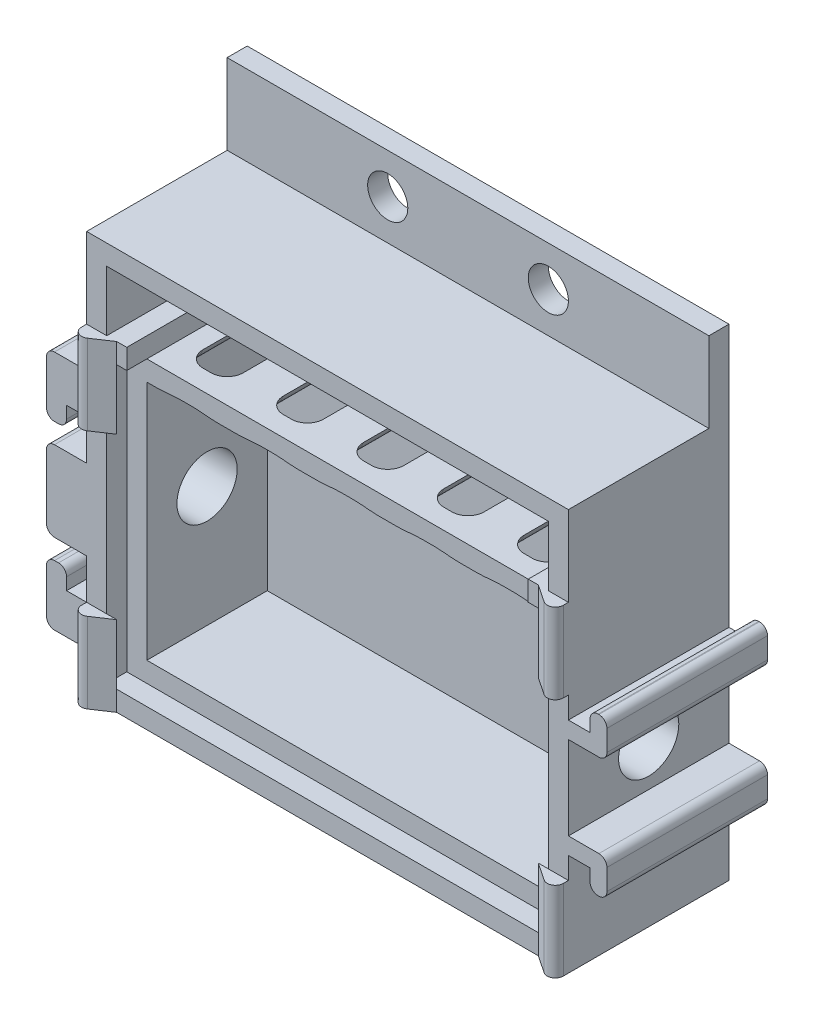
SolidWorks part; units mm, degrees
ref_plane "Front Plane" through (0, 0, 0) normal (0, 0, 1) x (1, 0, 0)
ref_plane "Top Plane" through (0, 0, 0) normal (0, 1, 0) x (1, 0, 0)
ref_plane "Right Plane" through (0, 0, 0) normal (1, 0, 0) x (0, 0, -1)
sketch "Sketch1" plane through (0, 0, 0) normal (0, 0, 1) x (1, 0, 0)
  line L1 (0, 0) -> (76.2, 0)
  line L2 (0, 0) -> (0, 76.2)
  line L3 (0, 76.2) -> (76.2, 76.2)
  line L4 (76.2, 0) -> (76.2, 76.2)
  dimension "D1" = 76.2
  dimension "D2" = 76.2
extrude "Boss-Extrude1" add sketch "Sketch1" along normal blind 25.4
sketch "Sketch2" plane through (0, 0, 25.4) normal (0, 0, 1) x (1, 0, 0)
  line L0 (0, 76.2) -> (0, 0) construction
  line L1 (3.175, 3.175) -> (73.025, 3.175)
  line L2 (3.175, 3.175) -> (3.175, 47.625)
  line L3 (3.175, 47.625) -> (73.025, 47.625)
  line L4 (73.025, 3.175) -> (73.025, 47.625)
  line L5 (38.1, 0) -> (38.1, 76.2) construction
  line L6 (0, 0) -> (76.2, 0) construction
  line L7 (76.2, 76.2) -> (0, 76.2) construction
  dimension "D2" = 3.175
  dimension "D1" = 3.175
  dimension "D3" = 28.575
extrude "Cut-Extrude1" cut sketch "Sketch2" against normal blind 3.175
sketch "Sketch9" plane through (0, 0, 22.225) normal (0, 0, 1) x (1, 0, 0)
  line L4 (69.85, 44.45) -> (6.35, 44.45)
  line L5 (69.85, 44.45) -> (6.35, 44.45)
  line L8 (6.35, 44.45) -> (6.35, 6.35)
  line L9 (6.35, 6.35) -> (69.85, 6.35)
  line L10 (69.85, 6.35) -> (69.85, 44.45)
  line L12 (6.35, 44.45) -> (6.35, 6.35)
  line L13 (6.35, 6.35) -> (69.85, 6.35)
  line L14 (69.85, 6.35) -> (69.85, 44.45)
  dimension "D1" = 3.175
extrude "Cut-Extrude9" cut sketch "Sketch9" against normal blind 19.05
sketch "Sketch10" plane through (0, 0, 25.4) normal (0, 0, 1) x (1, 0, 0)
  line L0 (76.2, 0) -> (76.2, 76.2) construction
  line L1 (0, 76.2) -> (76.2, 76.2)
  line L2 (0, 76.2) -> (0, 63.5)
  line L3 (0, 63.5) -> (76.2, 63.5)
  line L4 (76.2, 76.2) -> (76.2, 63.5)
  dimension "D1" = 12.7
extrude "Cut-Extrude10" cut sketch "Sketch10" against normal blind 22.225
sketch "Sketch11" plane through (0, 0, 25.4) normal (0, 0, 1) x (1, 0, 0)
  line L0 (38.1, 63.5) -> (38.1, 47.625) construction
  line L1 (3.175, 60.325) -> (73.025, 60.325)
  line L2 (3.175, 60.325) -> (3.175, 50.8)
  line L3 (6.35, 50.8) -> (3.175, 50.8)
  line L4 (73.025, 60.325) -> (73.025, 50.8)
  line L5 (0, 63.5) -> (76.2, 63.5) construction
  line L6 (73.025, 47.625) -> (3.175, 47.625) construction
  line L7 (0, 63.5) -> (0, 0) construction
  line L8 (0, 63.5) -> (76.2, 63.5) construction
  line L9 (6.35, 47.625) -> (6.35, 50.8)
  line L10 (6.35, 47.625) -> (69.85, 47.625)
  line L11 (73.025, 50.8) -> (69.85, 50.8)
  line L12 (6.35, 111.125) -> (95.25, 60.325)
  line L13 (69.85, 47.625) -> (69.85, 50.8)
  line M10 (3.175, 47.625) -> (73.025, 47.625)
  dimension "D1" = 3.175
  dimension "D2" = 3.175
  dimension "D3" = 3.175
  dimension "D4" = 3.175
extrude "Cut-Extrude11" cut sketch "Sketch11" against normal blind 22.225 contours L12 L0 L10 L13 L11 L4 L1 | L0 L1 L2 L3 L9 M10
sketch "Sketch12" plane through (0, 0, 3.175) normal (0, 0, 1) x (1, 0, 0)
  line L0 (38.1, 63.5) -> (38.1, 76.2) construction
  line L1 (0, 63.5) -> (76.2, 63.5) construction
  line L2 (76.2, 76.2) -> (0, 76.2) construction
  line L3 (0, 76.2) -> (0, 63.5) construction
  circle A0 centre (25.4, 69.85) radius 3.175
  circle A1 centre (50.8, 69.85) radius 3.175
  point P8 (0, 69.85)
  dimension "D2" = 6.35
  dimension "D1" = 25.4
  dimension "D3" = 6.35
extrude "Cut-Extrude12" cut sketch "Sketch12" against normal up to next
sketch "Sketch13" plane through (0, 44.45, 0) normal (0, -1, 0) x (1, 0, 0)
  line L0 (6.35, 12.7) -> (69.85, 12.7) construction
  line L1 (12.065, 19.05) -> (13.335, 19.05)
  line L2 (9.525, 16.51) -> (9.525, 8.89)
  line L3 (12.065, 6.35) -> (13.335, 6.35)
  line L4 (15.875, 16.51) -> (15.875, 8.89)
  line L5 (6.35, 3.175) -> (6.35, 22.225) construction
  line L6 (69.85, 3.175) -> (69.85, 22.225) construction
  line L7 (28.575, 16.51) -> (28.575, 8.89)
  line L8 (22.225, 16.51) -> (22.225, 8.89)
  line L9 (24.765, 6.35) -> (26.035, 6.35)
  line L10 (24.765, 19.05) -> (26.035, 19.05)
  line L11 (41.275, 16.51) -> (41.275, 8.89)
  line L12 (34.925, 16.51) -> (34.925, 8.89)
  line L13 (37.465, 6.35) -> (38.735, 6.35)
  line L14 (37.465, 19.05) -> (38.735, 19.05)
  line L15 (53.975, 16.51) -> (53.975, 8.89)
  line L16 (47.625, 16.51) -> (47.625, 8.89)
  line L17 (50.165, 6.35) -> (51.435, 6.35)
  line L18 (50.165, 19.05) -> (51.435, 19.05)
  line L19 (66.675, 16.51) -> (66.675, 8.89)
  line L20 (60.325, 16.51) -> (60.325, 8.89)
  line L21 (62.865, 6.35) -> (64.135, 6.35)
  line L22 (62.865, 19.05) -> (64.135, 19.05)
  arc A0 (12.065, 19.05) -> (9.525, 16.51) centre (12.065, 16.51) ccw
  arc A1 (13.335, 19.05) -> (15.875, 16.51) centre (13.335, 16.51) cw
  arc A2 (13.335, 6.35) -> (15.875, 8.89) centre (13.335, 8.89) ccw
  arc A3 (9.525, 8.89) -> (12.065, 6.35) centre (12.065, 8.89) ccw
  arc A4 (26.035, 19.05) -> (28.575, 16.51) centre (26.035, 16.51) cw
  arc A5 (24.765, 19.05) -> (22.225, 16.51) centre (24.765, 16.51) ccw
  arc A6 (22.225, 8.89) -> (24.765, 6.35) centre (24.765, 8.89) ccw
  arc A7 (26.035, 6.35) -> (28.575, 8.89) centre (26.035, 8.89) ccw
  arc A8 (38.735, 19.05) -> (41.275, 16.51) centre (38.735, 16.51) cw
  arc A9 (37.465, 19.05) -> (34.925, 16.51) centre (37.465, 16.51) ccw
  arc A10 (34.925, 8.89) -> (37.465, 6.35) centre (37.465, 8.89) ccw
  arc A11 (38.735, 6.35) -> (41.275, 8.89) centre (38.735, 8.89) ccw
  arc A12 (51.435, 19.05) -> (53.975, 16.51) centre (51.435, 16.51) cw
  arc A13 (50.165, 19.05) -> (47.625, 16.51) centre (50.165, 16.51) ccw
  arc A14 (47.625, 8.89) -> (50.165, 6.35) centre (50.165, 8.89) ccw
  arc A15 (51.435, 6.35) -> (53.975, 8.89) centre (51.435, 8.89) ccw
  arc A16 (64.135, 19.05) -> (66.675, 16.51) centre (64.135, 16.51) cw
  arc A17 (62.865, 19.05) -> (60.325, 16.51) centre (62.865, 16.51) ccw
  arc A18 (60.325, 8.89) -> (62.865, 6.35) centre (62.865, 8.89) ccw
  arc A19 (64.135, 6.35) -> (66.675, 8.89) centre (64.135, 8.89) ccw
  dimension "D6" = 2.54
  dimension "D1" = 6.35
  dimension "D2" = 12.7
  dimension "D3" = 3.175
  dimension "D4" = 5
extrude "Cut-Extrude13" cut sketch "Sketch13" against normal up to next
fillet "Fillet3" radius 5.08 28 edges at (65.9311, 44.45, 7.0939) (61.0689, 44.45, 7.0939) (60.325, 44.45, 12.7) (61.0689, 44.45, 18.3061) (65.9311, 44.45, 18.3061) (53.2311, 44.45, 7.0939) (48.3689, 44.45, 7.0939) (47.625, 44.45, 12.7) (48.3689, 44.45, 18.3061) (53.2311, 44.45, 18.3061) (40.5311, 44.45, 7.0939) (35.6689, 44.45, 7.0939) (34.925, 44.45, 12.7) (35.6689, 44.45, 18.3061) (40.5311, 44.45, 18.3061) (27.8311, 44.45, 7.0939) (22.9689, 44.45, 7.0939) (22.225, 44.45, 12.7) (22.9689, 44.45, 18.3061) (27.8311, 44.45, 18.3061) (15.1311, 44.45, 7.0939) (10.2689, 44.45, 7.0939) (10.2689, 44.45, 18.3061) (15.1311, 44.45, 18.3061) (53.975, 44.45, 12.7) (41.275, 44.45, 12.7) (28.575, 44.45, 12.7) (15.875, 44.45, 12.7)
ref_plane "Plane1" through (38.1, 0, 0) normal (1, 0, 0) x (0, 0, -1)
ref_plane "Plane2" through (0, 25.4, 0) normal (0, 1, 0) x (1, 0, 0)
sketch "Sketch14" plane through (0, 0, 0) normal (-1, 0, 0) x (0, 0, 1)
  line L0 (25.4, 63.5) -> (25.4, 0) construction
  line L1 (25.4, 44.45) -> (0, 44.45)
  line L2 (25.4, 44.45) -> (25.4, 6.35)
  line L3 (25.4, 6.35) -> (0, 6.35)
  line L4 (0, 44.45) -> (0, 6.35)
  line L5 (0, 76.2) -> (0, 0) construction
  line L7 (25.4, 25.4) -> (0, 25.4) construction
  line L10 (10.4775, 25.4) -> (-10.4775, 25.4) construction
  dimension "D1" = 38.1
extrude "Boss-Extrude2" add sketch "Sketch14" along normal blind 6.35
sketch "Sketch15" plane through (-6.35, 0, 0) normal (-1, 0, 0) x (0, 0, 1)
  line L0 (0, 25.4) -> (25.4, 25.4) construction
  line L1 (0, 44.45) -> (0, 6.35) construction
  line L2 (25.4, 6.35) -> (25.4, 44.45) construction
  line L3 (12.7, 6.35) -> (12.7, 44.45) construction
  line L4 (0, 6.35) -> (25.4, 6.35) construction
  line L5 (25.4, 44.45) -> (0, 44.45) construction
  circle A0 centre (12.7, 25.4) radius 4.7625
  dimension "D1" = 9.525
extrude "Cut-Extrude14" cut sketch "Sketch15" against normal up to next
mirror "Mirror1" about plane through (38.1, 0, 0) normal (1, 0, 0) of "Cut-Extrude14", "Boss-Extrude2"
sketch "Sketch16" plane through (0, 0, 25.4) normal (0, 0, 1) x (1, 0, 0)
  line L0 (-6.35, 19.05) -> (0, 19.05)
  line L1 (-6.35, 6.35) -> (-6.35, 44.45) construction
  line L2 (-6.35, 6.35) -> (0, 6.35) construction
  line L3 (0, 19.05) -> (0, 12.7)
  line L4 (-3.175, 15.875) -> (-3.175, 12.7)
  line L5 (-3.175, 12.7) -> (0, 12.7)
  line L6 (-3.175, 15.875) -> (-6.35, 15.875)
  line L7 (-6.35, 15.875) -> (-6.35, 19.05)
  line L8 (82.55, 19.05) -> (76.2, 19.05)
  line L9 (82.55, 6.35) -> (82.55, 44.45) construction
  line L10 (76.2, 6.35) -> (76.2, 15.875)
  line L11 (76.2, 15.875) -> (79.375, 15.875)
  line L12 (79.375, 12.7) -> (79.375, 15.875)
  line L13 (79.375, 12.7) -> (82.55, 12.7)
  line L14 (82.55, 6.35) -> (82.55, 12.7)
  line L17 (82.55, 6.35) -> (76.2, 6.35)
  line L18 (82.55, 25.4) -> (76.2, 25.4)
  line L19 (76.2, 25.4) -> (76.2, 19.05)
  line L20 (82.55, 19.05) -> (82.55, 25.4)
  dimension "D1" = 12.7
  dimension "D2" = 6.35
  dimension "D3" = 3.175
  dimension "D4" = 3.175
  dimension "D5" = 6.35
  dimension "D6" = 3.175
  dimension "D7" = 3.175
extrude "Cut-Extrude15" cut sketch "Sketch16" against normal up to next
sketch "Sketch17" plane through (0, 0, 25.4) normal (0, 0, 1) x (1, 0, 0)
  line L62 (76.2, 16.129) -> (76.2, 15.875)
  line L63 (76.2, 15.875) -> (79.375, 15.875)
  line L64 (79.375, 15.875) -> (79.375, 12.7)
  line L65 (79.375, 12.7) -> (82.55, 12.7)
  line L66 (82.55, 12.7) -> (82.55, 19.05)
  line L67 (79.629, 16.129) -> (76.2, 16.129)
  line L68 (76.2, 18.796) -> (82.296, 18.796)
  line L69 (82.296, 18.796) -> (82.296, 12.954)
  line L70 (82.296, 12.954) -> (79.629, 12.954)
  line L71 (79.629, 12.954) -> (79.629, 16.129)
  line L72 (79.629, 16.129) -> (76.2, 16.129)
  line L73 (76.2, 18.796) -> (82.296, 18.796)
  line L74 (82.296, 18.796) -> (82.296, 12.954)
  line L75 (82.296, 12.954) -> (79.629, 12.954)
  line L76 (79.629, 12.954) -> (79.629, 16.129)
  line L77 (82.55, 19.05) -> (76.2, 19.05)
  line L78 (76.2, 19.05) -> (76.2, 18.796)
  dimension "D1" = 0.254
extrude "Cut-Extrude16" cut sketch "Sketch17" against normal up to next
mirror "Mirror2" about plane through (0, 25.4, 0) normal (0, 1, 0) of "Cut-Extrude16", "Cut-Extrude15"
fillet "Fillet5" radius 1.27 14 edges at (79.629, 37.846, 12.7) (82.296, 37.846, 12.7) (82.296, 32.004, 12.7) (82.296, 18.796, 12.7) (79.629, 12.954, 12.7) (82.296, 12.954, 12.7) (-3.175, 34.925, 12.7) (-6.35, 44.45, 12.7) (-6.35, 34.925, 12.7) (-6.35, 31.75, 12.7) (-6.35, 19.05, 12.7) (-6.35, 6.35, 12.7) (-3.175, 15.875, 12.7) (-6.35, 15.875, 12.7)
sketch "Sketch18" plane through (0, 0, 0) normal (1, 0, 0) x (0, 0, -1)
  line L1 (-25.4, 0) -> (-28.575, 0)
  line L2 (-25.4, 0) -> (-25.4, 12.7)
  line L3 (-25.4, 12.7) -> (-28.575, 12.7)
  line L4 (-28.575, 0) -> (-28.575, 12.7)
  dimension "D1" = 12.7
  dimension "D2" = 3.175
extrude "Boss-Extrude3" add sketch "Sketch18" along normal blind 4.7625
sketch "Sketch19" plane through (0, 0, 0) normal (0, -1, 0) x (1, 0, 0)
  line L0 (0, 28.575) -> (4.7625, 25.4)
  line L1 (4.7625, 25.4) -> (4.7625, 28.575)
  line L2 (4.7625, 28.575) -> (0, 28.575)
extrude "Cut-Extrude17" cut sketch "Sketch19" against normal up to next
mirror "Mirror3" about plane through (38.1, 0, 0) normal (1, 0, 0) of "Cut-Extrude17", "Boss-Extrude3"
mirror "Mirror4" about plane through (0, 25.4, 0) normal (0, 1, 0) of "Mirror3", "Boss-Extrude3", "Cut-Extrude17"
fillet "Fillet6" radius 1.27 4 edges at (0, 6.35, 28.575) (76.2, 6.35, 28.575) (76.2, 44.45, 28.575) (0, 44.45, 28.575)
